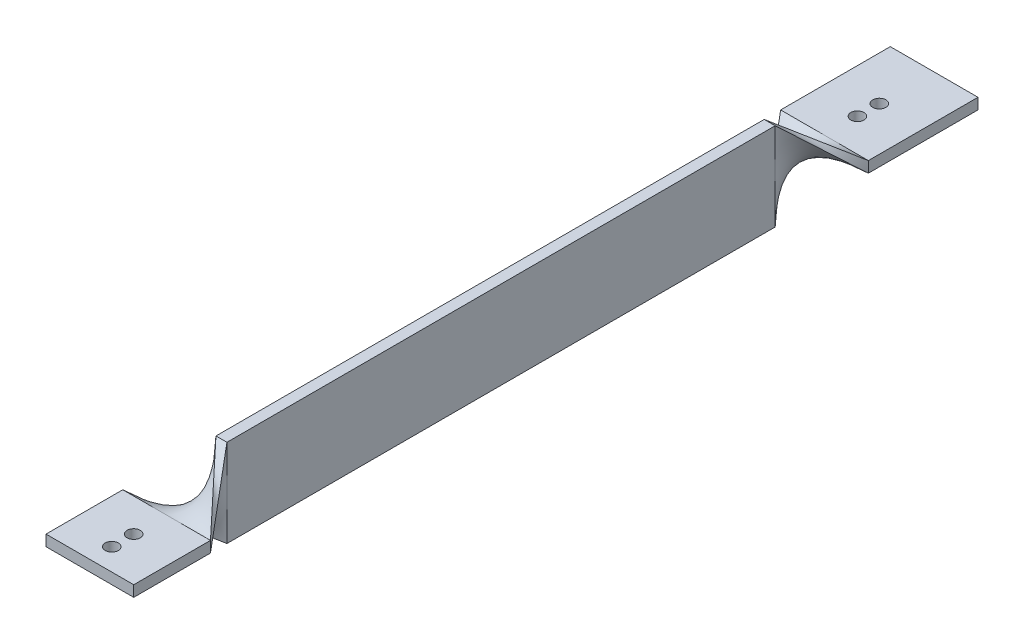
SolidWorks part; units mm, degrees
ref_plane "Płaszczyzna przednia" through (0, 0, 0) normal (0, 0, 1) x (1, 0, 0)
ref_plane "Płaszczyzna górna" through (0, 0, 0) normal (0, 1, 0) x (1, 0, 0)
ref_plane "Płaszczyzna prawa" through (0, 0, 0) normal (1, 0, 0) x (0, 0, -1)
sketch "Szkic1" plane through (0, 0, 0) normal (0, 0, 1) x (1, 0, 0)
  line L1 (0, 0) -> (40, 0)
  line L2 (0, 0) -> (0, 5)
  line L3 (0, 5) -> (40, 5)
  line L4 (40, 0) -> (40, 5)
  dimension "D1" = 40
  dimension "D2" = 5
extrude "Dodanie-wyciągnięcie1" add sketch "Szkic1" along normal mid plane 50
ref_plane "Płaszczyzna1" through (0, 0, 50) normal (0, 0, 1) x (1, 0, 0)
sketch "Szkic2" plane through (0, 0, 50) normal (0, 0, 1) x (1, 0, 0)
  line L0 (0, 5) -> (0, 0) construction
  line L1 (17.5, 22.5) -> (22.5, 22.5)
  line L2 (17.5, 22.5) -> (17.5, -17.5)
  line L3 (17.5, -17.5) -> (22.5, -17.5)
  line L4 (22.5, 22.5) -> (22.5, -17.5)
  line L5 (0, 0) -> (40, 0) construction
  dimension "D1" = 5
  dimension "D2" = 40
  dimension "D3" = 17.5
  dimension "D4" = 17.5
extrude "Dodanie-wyciągnięcie2" add sketch "Szkic2" along normal blind 250 separate body
loft "Wyciągnięcie po profilach3" add section face at (20, 2.5, 25) section face at (20, 2.5, 50) connector at (40, 0, 25) connector at (22.5, 22.5, 50)
ref_plane "Płaszczyzna2" through (0, 0, 325) normal (0, 0, 1) x (1, 0, 0)
sketch "Szkic5" plane through (0, 0, 325) normal (0, 0, 1) x (1, 0, 0)
  line L1 (0, 5) -> (40, 5)
  line L2 (0, 5) -> (0, 0)
  line L3 (0, 0) -> (40, 0)
  line L4 (40, 5) -> (40, 0)
extrude "Dodanie-wyciągnięcie3" add sketch "Szkic5" along normal blind 35 separate body
loft "Wyciągnięcie po profilach5" add section face at (20, 2.5, 325) section face at (20, 2.5, 300) connector at (40, 0, 325) connector at (22.5, 22.5, 300)
sketch "Szkic7" plane through (0, 5, 0) normal (0, 1, 0) x (1, 0, 0)
  line L0 (40, -360) -> (40, -325) construction
  line L1 (-55, -325) -> (55, -325) construction
  circle A0 centre (20, -340) radius 3
  circle A1 centre (20, -350) radius 3
  dimension "D1" = 6
  dimension "D2" = 20
  dimension "D5" = 20
  dimension "D6" = 6
  dimension "D3" = 15
  dimension "D4" = 10
sketch "Szkic8" plane through (0, 5, 0) normal (0, 1, 0) x (1, 0, 0)
  line L0 (40, -25) -> (0, -25) construction
  line L1 (40, -25) -> (40, 25) construction
  line L2 (0, -25) -> (0, 25) construction
  circle A0 centre (20, -10) radius 3
  circle A2 centre (20, 0) radius 3
  dimension "D1" = 6
  dimension "D2" = 15
  dimension "D3" = 20
  dimension "D4" = 6
  dimension "D5" = 10
  dimension "D6" = 20
sketch "Szkic12" plane through (0, 5, 0) normal (0, 1, 0) x (1, 0, 0)
extrude "Wytnij-wyciągnięcie3" cut sketch "Szkic7" against normal blind 20 contours A1 | A0
extrude "Wytnij-wyciągnięcie4" cut sketch "Szkic8" against normal blind 20 contours A2 | A0
